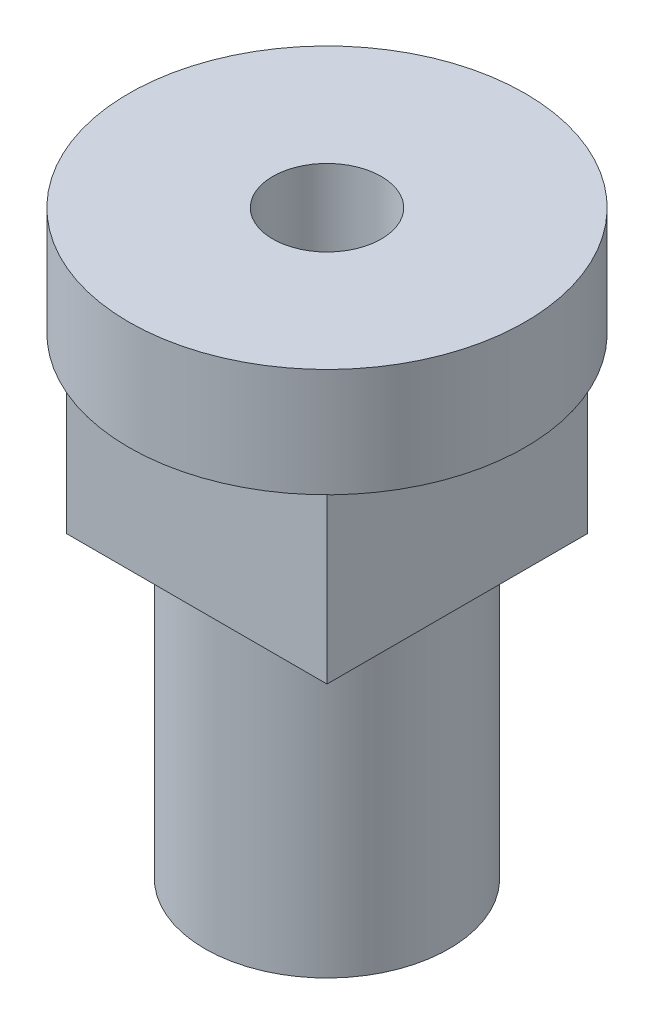
SolidWorks part; units mm, degrees
ref_plane "Front Plane" through (0, 0, 0) normal (0, 0, 1) x (1, 0, 0)
ref_plane "Top Plane" through (0, 0, 0) normal (0, 1, 0) x (1, 0, 0)
ref_plane "Right Plane" through (0, 0, 0) normal (1, 0, 0) x (0, 0, -1)
sketch "Sketch1" plane through (0, 0, 0) normal (0, 1, 0) x (1, 0, 0)
  line L1 (-4.8, -4.8) -> (4.8, -4.8)
  line L2 (-4.8, -4.8) -> (-4.8, 4.8)
  line L3 (-4.8, 4.8) -> (4.8, 4.8)
  line L4 (4.8, -4.8) -> (4.8, 4.8)
  line L5 (-4.8, -4.8) -> (4.8, 4.8) construction
  line L6 (-4.8, 4.8) -> (4.8, -4.8) construction
  circle A0 centre (0, 0) radius 4.5
  circle A1 centre (0, 0) radius 2
  circle A2 centre (0, 0) radius 7.3
  dimension "D1" = 9
  dimension "D3" = 4
  dimension "D4" = 14.6
  dimension "D2" = 9.6
extrude "Boss-Extrude1" add sketch "Sketch1" along normal blind 11 contours A0 A1 | A1 region at (-4.3727, 0, 0) region at (0, 0, 0)
extrude "Boss-Extrude2" add sketch "Sketch1<3>" along normal blind 6.4 from surface contours L1 L4 L3 L2 A0 | A0 A1 | A1 region at (-4.6642, 0, 0) region at (-4.3727, 0, 0) region at (0, 0, 0) starting at face at (0, 11, 4.5)
sketch "Sketch1<3>" plane through (0, 0, 0) normal (0, 1, 0) x (1, 0, 0) same geometry as "Sketch1"
extrude "Boss-Extrude3" add sketch "Sketch1<4>" along normal blind 4 from surface contours A2 L4 L1 L2 L3 | L1 L4 L3 L2 A0 | A0 A1 | A1 region at (-4.6642, 0, 0) region at (-4.3727, 0, 0) region at (0, 0, 0) region at (-7.0935, 0, 0) starting at face at (0, 17.4, 0)
sketch "Sketch1<4>" plane through (0, 0, 0) normal (0, 1, 0) x (1, 0, 0) same geometry as "Sketch1"
extrude "Cut-Extrude1" cut sketch "Sketch1<5>" against normal blind 10 from surface contours A1 region at (0, 0, 0) starting at face at (0, 21.4, -7.3)
sketch "Sketch1<5>" plane through (0, 0, 0) normal (0, 1, 0) x (1, 0, 0) same geometry as "Sketch1"
